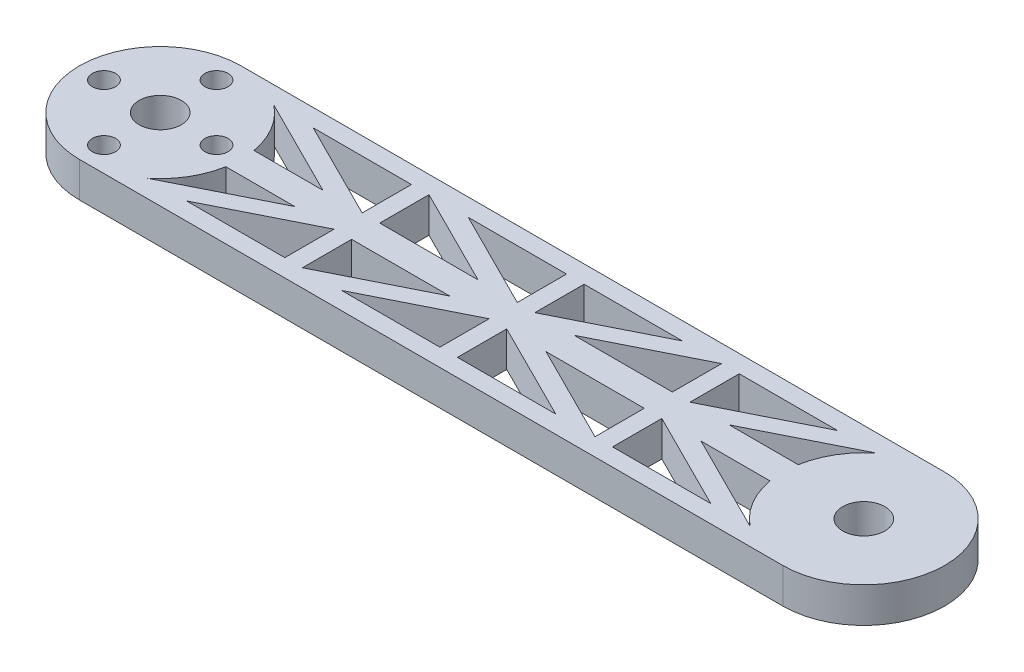
SolidWorks part; units mm, degrees
ref_plane "Front Plane" through (0, 0, 0) normal (0, 0, 1) x (1, 0, 0)
ref_plane "Top Plane" through (0, 0, 0) normal (0, 1, 0) x (1, 0, 0)
ref_plane "Right Plane" through (0, 0, 0) normal (1, 0, 0) x (0, 0, -1)
sketch "Sketch1" plane through (0, 0, 0) normal (0, 1, 0) x (1, 0, 0)
  line L0 (-50, 0) -> (50, 0) construction
  line L1 (-50, 11.5) -> (50, 11.5)
  line L2 (-50, -11.5) -> (50, -11.5)
  arc A0 (-50, 11.5) -> (-50, -11.5) centre (-50, 0) ccw
  arc A1 (50, -11.5) -> (50, 11.5) centre (50, 0) ccw
  circle A2 centre (-50, 8) radius 1.65
  circle A3 centre (-42, 0) radius 1.65
  circle A4 centre (-50, -8) radius 1.65
  circle A5 centre (-58, 0) radius 1.65
  circle A6 centre (50, 0) radius 3
  circle A7 centre (-50, 0) radius 3
  point P2 (0, 0)
  point P11 (-50, 0)
  point P20 (-50, 0)
  dimension "D1" = 11.5
  dimension "D3" = 3.3
  dimension "D6" = 6
  dimension "D7" = 6
  dimension "D2" = 100
  dimension "D4" = 8
  dimension "D5" = 4
extrude "Boss-Extrude1" add sketch "Sketch1" along normal blind 5
sketch "Sketch2" plane through (0, 5, 0) normal (0, 1, 0) x (1, 0, 0)
  line L0 (-50, 0) -> (50, 0) construction
  line L2 (-38.6752, 2) -> (-28.8749, 2)
  line L3 (-28.8749, 2) -> (-42.8411, 9)
  line L4 (-37.2617, 9) -> (-23.2955, 2)
  line L5 (-23.2955, 2) -> (-23.2955, 9)
  line L6 (-23.2955, 9) -> (-37.2617, 9)
  line L7 (50, 11.5) -> (-50, 11.5) construction
  line L8 (-6.8294, 2) -> (-20.7955, 9)
  line L9 (-20.7955, 9) -> (-20.7955, 2)
  line L10 (-20.7955, 2) -> (-6.8294, 2)
  line L11 (-1.25, 9) -> (-15.2162, 9)
  line L12 (-15.2162, 9) -> (-1.25, 2)
  line L13 (-1.25, 2) -> (-1.25, 9)
  line L14 (-28.8749, 2) -> (-6.8294, 2) construction
  line L15 (-1.25, -2) -> (-1.25, -9)
  line L16 (-15.2162, -9) -> (-1.25, -2)
  line L17 (-1.25, -9) -> (-15.2162, -9)
  line L18 (-20.7955, -2) -> (-6.8294, -2)
  line L19 (-20.7955, -9) -> (-20.7955, -2)
  line L20 (-6.8294, -2) -> (-20.7955, -9)
  line L21 (-23.2955, -2) -> (-23.2955, -9)
  line L22 (-37.2617, -9) -> (-23.2955, -2)
  line L23 (-23.2955, -9) -> (-37.2617, -9)
  line L24 (-28.8749, -2) -> (-42.8411, -9)
  line L25 (-38.6752, -2) -> (-28.8749, -2)
  line L26 (0, 0) -> (0, 11.5) construction
  line L27 (15.2162, -9) -> (1.25, -2)
  line L28 (1.25, -9) -> (15.2162, -9)
  line L29 (1.25, -2) -> (1.25, -9)
  line L30 (20.7955, -9) -> (20.7955, -2)
  line L31 (6.8294, -2) -> (20.7955, -9)
  line L32 (20.7955, -2) -> (6.8294, -2)
  line L33 (37.2617, -9) -> (23.2955, -2)
  line L34 (23.2955, -9) -> (37.2617, -9)
  line L35 (23.2955, -2) -> (23.2955, -9)
  line L36 (28.8749, -2) -> (42.8411, -9)
  line L37 (38.6752, -2) -> (28.8749, -2)
  line L38 (28.8749, 2) -> (42.8411, 9)
  line L39 (38.6752, 2) -> (28.8749, 2)
  line L40 (23.2955, 2) -> (23.2955, 9)
  line L41 (37.2617, 9) -> (23.2955, 2)
  line L42 (23.2955, 9) -> (37.2617, 9)
  line L43 (20.7955, 2) -> (6.8294, 2)
  line L44 (20.7955, 9) -> (20.7955, 2)
  line L45 (6.8294, 2) -> (20.7955, 9)
  line L46 (1.25, 2) -> (1.25, 9)
  line L47 (15.2162, 9) -> (1.25, 2)
  line L48 (1.25, 9) -> (15.2162, 9)
  circle A0 centre (-50, 0) radius 11.5 construction
  arc A1 (-42.8411, 9) -> (-38.6752, 2) centre (-50, 0) cw
  arc A2 (-42.8411, -9) -> (-38.6752, -2) centre (-50, 0) ccw
  arc A3 (42.8411, -9) -> (38.6752, -2) centre (50, 0) cw
  arc A4 (42.8411, 9) -> (38.6752, 2) centre (50, 0) ccw
  dimension "D1" = 1.25
  dimension "D2" = 2.5
  dimension "D3" = 2.5
  dimension "D4" = 2
  dimension "D6" = 2.5
  dimension "D5" = 2
extrude "Cut-Extrude1" cut sketch "Sketch2" against normal blind 5
